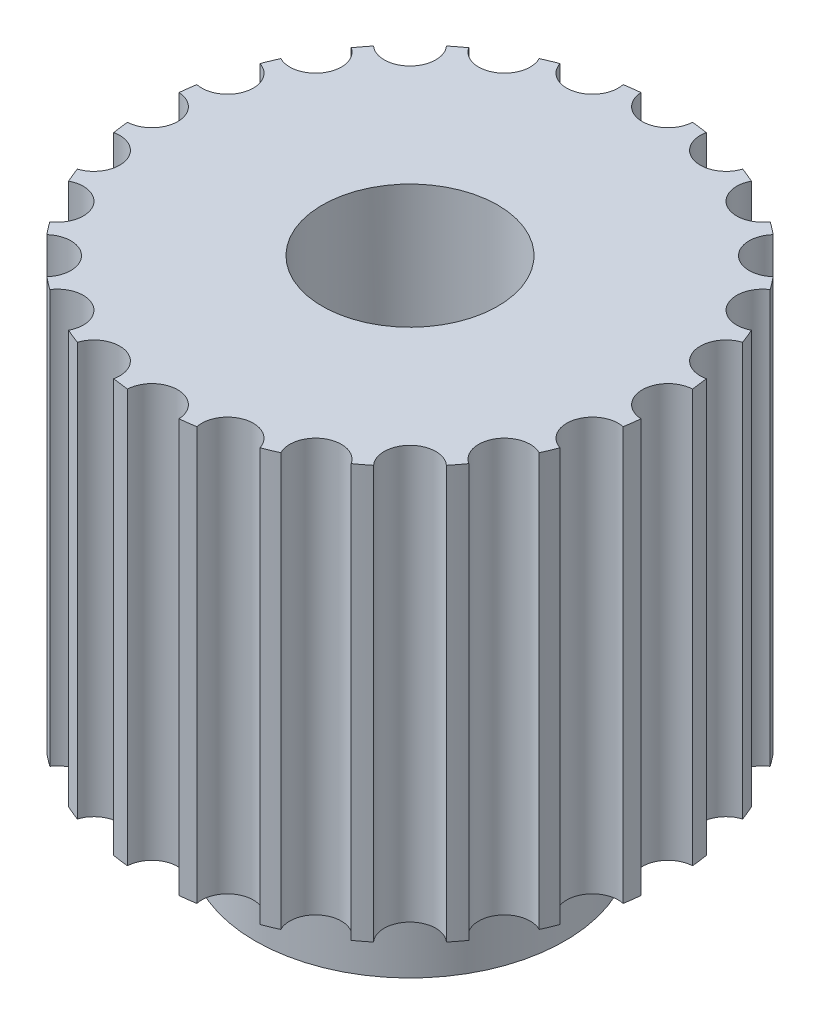
SolidWorks part; units mm, degrees
ref_plane "Front Plane" through (0, 0, 0) normal (0, 0, 1) x (1, 0, 0)
ref_plane "Top Plane" through (0, 0, 0) normal (0, 1, 0) x (1, 0, 0)
ref_plane "Right Plane" through (0, 0, 0) normal (1, 0, 0) x (0, 0, -1)
sketch "Sketch2" plane through (0, 0, 0) normal (0, 0, 1) x (1, 0, 0)
  line L0 (0, -5) -> (0, 5)
  line L1 (-3, -5) -> (3, -5)
  line L2 (-3, -5) -> (-3, 5)
  line L3 (-3, 5) -> (3, 5)
  line L4 (3, -5) -> (3, 5)
  line L5 (-3, -5) -> (3, 5) construction
  line L6 (-3, 5) -> (3, -5) construction
  line L7 (-5, -3) -> (5, -3)
  line L8 (-5, -3) -> (-5, 5)
  line L9 (-5, 5) -> (5, 5)
  line L10 (5, -3) -> (5, 5)
  line L11 (-5, -3) -> (5, 5) construction
  line L12 (-5, 5) -> (5, -3) construction
  line L13 (-1.7, -5) -> (1.7, -5)
  line L14 (-1.7, -5) -> (-1.7, 5)
  line L15 (-1.7, 5) -> (1.7, 5)
  line L16 (1.7, -5) -> (1.7, 5)
  line L17 (-1.7, -5) -> (1.7, 5) construction
  line L18 (-1.7, 5) -> (1.7, -5) construction
  point P0 (0, 0)
  point P6 (0, 1)
  point P13 (0, 0)
  dimension "D1" = 6
  dimension "D2" = 8
  dimension "D3" = 2
  dimension "D4" = 10
  dimension "D5" = 3.4
revolve "Revolve2" add sketch "Sketch2" angle 360 about L0 region at (2.35, -4, 0) region at (2.35, 1, 0) region at (4, 1, 0)
sketch "Sketch3" plane through (0, 0, 0) normal (1, 0, 0) x (0, 0, -1)
  line L0 (-5, -3) -> (5, 5) construction
  circle A0 centre (0, 1) radius 3
  dimension "D1" = 6
extrude "Cut-Extrude2" cut sketch "Sketch3" against normal blind 2 from offset 3 offset against normal yes
hole_wizard "M3x0.5 Tapped Hole1" positions "Sketch4" profile "Sketch5" tap size "M3x0.5" standard "ANSI Metric"
sketch "Sketch4" plane through (-3, 0, 0) normal (-1, 0, 0) x (0, 0, 1)
  circle A2 centre (0, 1) radius 3
  circle A3 centre (0, 1) radius 3
  point P5 (0, 1)
  dimension "D1" = 0
cosmetic thread "Hole Thread1" parameters "D2"=3
sketch "Sketch5" plane through (-3, 1, 0) normal (0, 1, 0) x (0, 0, 1)
  line L0 (0, 0) -> (0, 3.7511)
  line L1 (0, 3.7511) -> (1.25, 3)
  line L2 (1.25, 3) -> (1.25, 0)
  line L5 (1.25, 0) -> (0, 0)
  line L10 (0, 3.7511) -> (-1.25, 3) construction
  line L11 (0, -6.35) -> (0, 107.95) construction
  dimension "Tap Drill Dia." = 2.5
  dimension "Tap Drill Depth" = 3
  dimension "Drill Angle" = 118
sketch "Sketch6" plane through (0, 5, 0) normal (0, 1, 0) x (1, 0, 0)
  line L0 (0, 0) -> (0, 5)
  circle A0 centre (0, 0) radius 5 construction
  circle A1 centre (0, 5) radius 0.5
  circle M1 centre (0, 0) radius 5
  dimension "D1" = 1
extrude "Cut-Extrude3" cut sketch "Sketch6" against normal through all contours A1 L0 M1 | L0 A1 M1 region at (-0.2087, 5, -4.7834) region at (0.2087, 5, -4.7834)
pattern_circular "CirPattern1" count 24 every 15 about axis through (0, 5, 0) along (0, -1, 0) of "Cut-Extrude3"
